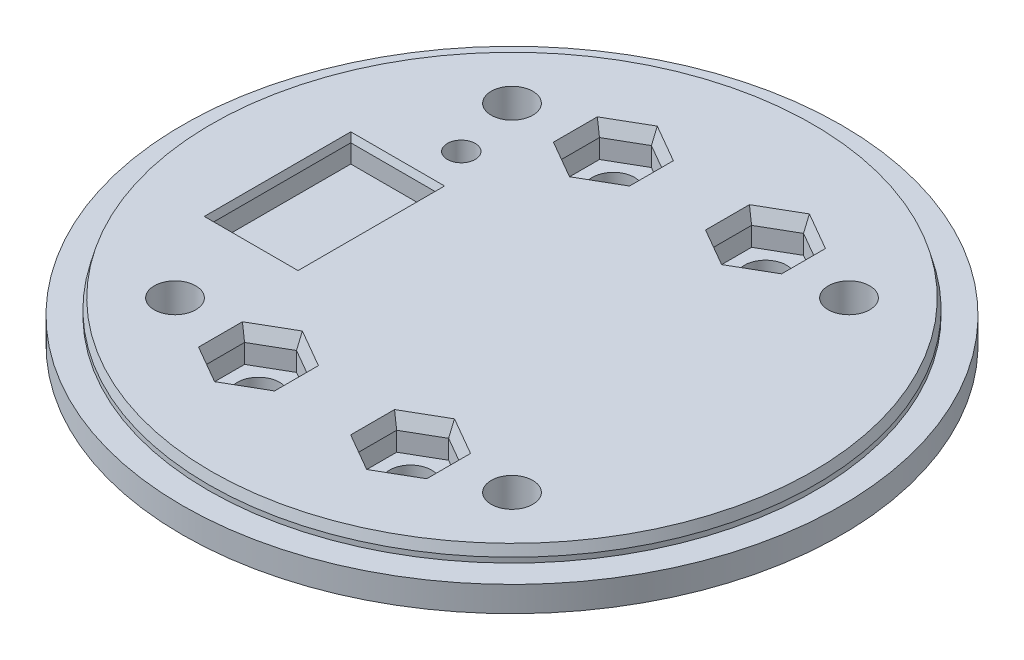
SolidWorks part; units mm, degrees
ref_plane "Спереди" through (0, 0, 0) normal (0, 0, 1) x (1, 0, 0)
ref_plane "Сверху" through (0, 0, 0) normal (0, 1, 0) x (1, 0, 0)
ref_plane "Справа" through (0, 0, 0) normal (1, 0, 0) x (0, 0, -1)
sketch "Эскиз1" plane through (0, 0, 0) normal (0, 1, 0) x (1, 0, 0)
  circle A0 centre (0, 0) radius 65
  dimension "D1" = 130
extrude "Бобышка-Вытянуть1" add sketch "Эскиз1" along normal blind 5
sketch "Эскиз2" plane through (0, 5, 0) normal (0, 1, 0) x (1, 0, 0)
  circle A0 centre (0, 0) radius 59.85
  dimension "D1" = 119.7
extrude "Бобышка-Вытянуть2" add sketch "Эскиз2" along normal blind 3
sketch "Эскиз3" plane through (0, 0, 0) normal (0, -1, 0) x (1, 0, 0)
  line L1 (25, -25) -> (-25, -25)
  line L2 (25, -25) -> (25, 25)
  line L3 (25, 25) -> (-25, 25)
  line L4 (-25, -25) -> (-25, 25)
  line L5 (25, -25) -> (-25, 25) construction
  line L6 (25, 25) -> (-25, -25) construction
  point P0 (0, 0)
  dimension "D1" = 50
  dimension "D2" = 50
extrude "Бобышка-Вытянуть3" add sketch "Эскиз3" along normal blind 25
sketch "Эскиз5" plane through (0, 0, 0) normal (0, -1, 0) x (1, 0, 0)
  line L1 (33.234, -33.234) -> (-33.234, -33.234) construction
  line L2 (33.234, -33.234) -> (33.234, 33.234) construction
  line L3 (33.234, 33.234) -> (-33.234, 33.234) construction
  line L4 (-33.234, -33.234) -> (-33.234, 33.234) construction
  line L5 (33.234, -33.234) -> (-33.234, 33.234) construction
  line L6 (33.234, 33.234) -> (-33.234, -33.234) construction
  circle A1 centre (33.234, -33.234) radius 4.1
  circle A2 centre (-33.234, -33.234) radius 4.1
  circle A3 centre (-33.234, 33.234) radius 4.1
  circle A4 centre (33.234, 33.234) radius 4.1
  circle A5 centre (0, 0) radius 47 construction
  point P0 (0, 0)
  dimension "D1" = 94
  dimension "D2" = 8.2
extrude "Вырез-Вытянуть2" cut sketch "Эскиз5" against normal through all
sketch "Эскиз6" plane through (0, 8, 0) normal (0, 1, 0) x (1, 0, 0)
  line L0 (0, 0) -> (0, 52.4) construction
  line L1 (0, 20) -> (-30, 20) construction
  circle A0 centre (0, 0) radius 59.85 construction
  circle A1 centre (-30, 20) radius 2.75
  dimension "D3" = 5.5
  dimension "D1" = 20
  dimension "D2" = 30
extrude "Вырез-Вытянуть3" cut sketch "Эскиз6" against normal through all
sketch "Sketch2" plane through (-25, 0, 0) normal (-1, 0, 0) x (0, 0, 1)
  line L0 (-25, -25) -> (25, 0) construction
  line L2 (10.125, -17.675) -> (-10.125, -17.675)
  line L3 (10.125, -17.675) -> (10.125, -7.325)
  line L4 (10.125, -7.325) -> (-10.125, -7.325)
  line L5 (-10.125, -17.675) -> (-10.125, -7.325)
  line L6 (10.125, -17.675) -> (-10.125, -7.325) construction
  line L7 (10.125, -7.325) -> (-10.125, -17.675) construction
  point P2 (0, -12.5)
  point P10 (0, -12.5)
  dimension "D1" = 20.25
  dimension "D2" = 10.35
extrude "Cut-Extrude1" cut sketch "Sketch2" against normal through all
chamfer "Chamfer1" distance 2 angle 15 1 edges at (0, 8, 59.85) first distance on face at (0, 8, 59.85)
sketch "Sketch4" plane through (0, -25, 0) normal (0, -1, 0) x (1, 0, 0)
  line L0 (-25, 0) -> (25, 0) construction
  line L1 (-25, 25) -> (-25, -25) construction
  line L2 (25, -25) -> (25, 25) construction
  line L4 (25, -25) -> (-25, -25)
  line L5 (25, -25) -> (25, 25)
  line L6 (25, 25) -> (-25, 25)
  line L7 (-25, -25) -> (-25, 25)
  line L8 (25, -25) -> (-25, 25) construction
  line L9 (25, 25) -> (-25, -25) construction
  point P6 (0, 0)
extrude "Cut-Extrude3" cut sketch "Sketch4" against normal blind 12.5
sketch "Sketch5" plane through (0, -7.325, 0) normal (0, -1, 0) x (1, 0, 0)
  line L0 (0, 10.125) -> (0, -10.125) construction
  line L1 (25, 10.125) -> (-25, 10.125) construction
  line L2 (25, -10.125) -> (-25, -10.125) construction
  line L4 (25, -45) -> (-25, -45)
  line L5 (25, -45) -> (25, 45)
  line L6 (25, 45) -> (-25, 45)
  line L7 (-25, -45) -> (-25, 45)
  line L8 (25, -45) -> (-25, 45) construction
  line L9 (25, 45) -> (-25, -45) construction
  point P6 (0, 0)
  dimension "D1" = 50
  dimension "D2" = 90
extrude "Boss-Extrude2" add sketch "Sketch5" against normal up to surface (7.325 mm away) from offset 2 up to face at (-30, 0, -17.25) offset against normal yes
sketch "Sketch6" plane through (0, -5.325, 0) normal (0, -1, 0) x (1, 0, 0)
  line L0 (25, 35) -> (-25, 35) construction
  line L1 (25, 25) -> (25, 45) construction
  line L2 (-25, 45) -> (-25, 25) construction
  line L3 (25, -35) -> (-25, -35) construction
  line L4 (25, -45) -> (25, -25) construction
  line L5 (-25, -25) -> (-25, -45) construction
  line L6 (0, 45) -> (0, -45) construction
  line L7 (25, 45) -> (-25, 45) construction
  line L8 (-25, -45) -> (25, -45) construction
  line L9 (-15, 35) -> (15, -35) construction
  line L10 (-15, -35) -> (15, 35) construction
  circle A0 centre (-15, 35) radius 4.15
  circle A1 centre (-15, -35) radius 4.15
  circle A2 centre (15, 35) radius 4.15
  circle A3 centre (15, -35) radius 4.15
  point P21 (0, 0)
  point P31 (0, 0)
  dimension "D3" = 8.3
  dimension "D1" = 10
  dimension "D2" = 10
  dimension "D4" = 30
  dimension "D5" = 70
  dimension "D6" = 70
extrude "Cut-Extrude4" cut sketch "Sketch6" against normal through all
sketch "Sketch7" plane through (0, 8, 0) normal (0, 1, 0) x (1, 0, 0)
  line L1 (-15, -42.5) -> (-8.5048, -38.75)
  line L2 (-8.5048, -38.75) -> (-8.5048, -31.25)
  line L3 (-8.5048, -31.25) -> (-15, -27.5)
  line L4 (-15, -27.5) -> (-21.4952, -31.25)
  line L5 (-21.4952, -31.25) -> (-21.4952, -38.75)
  line L6 (-21.4952, -38.75) -> (-15, -42.5)
  line L7 (-15, 27.5) -> (-8.5048, 31.25)
  line L8 (-8.5048, 31.25) -> (-8.5048, 38.75)
  line L9 (-8.5048, 38.75) -> (-15, 42.5)
  line L10 (-15, 42.5) -> (-21.4952, 38.75)
  line L11 (-21.4952, 38.75) -> (-21.4952, 31.25)
  line L12 (-21.4952, 31.25) -> (-15, 27.5)
  line L13 (15, -42.5) -> (21.4952, -38.75)
  line L14 (21.4952, -38.75) -> (21.4952, -31.25)
  line L15 (21.4952, -31.25) -> (15, -27.5)
  line L16 (15, -27.5) -> (8.5048, -31.25)
  line L17 (8.5048, -31.25) -> (8.5048, -38.75)
  line L18 (8.5048, -38.75) -> (15, -42.5)
  line L19 (15, 27.5) -> (21.4952, 31.25)
  line L20 (21.4952, 31.25) -> (21.4952, 38.75)
  line L21 (21.4952, 38.75) -> (15, 42.5)
  line L22 (15, 42.5) -> (8.5048, 38.75)
  line L23 (8.5048, 38.75) -> (8.5048, 31.25)
  line L24 (8.5048, 31.25) -> (15, 27.5)
  circle A0 centre (-15, -35) radius 7.5 construction
  circle A1 centre (-15, 35) radius 7.5 construction
  circle A2 centre (15, -35) radius 7.5 construction
  circle A3 centre (15, 35) radius 7.5 construction
  dimension "D1" = 15
extrude "Cut-Extrude5" cut sketch "Sketch7" against normal blind 6.5
chamfer "Chamfer2" distance 1 angle 70 24 edges at (-11.7524, 8, 29.375) (-8.5048, 8, 35) (-11.7524, 8, 40.625) (-18.2476, 8, 40.625) (-21.4952, 8, 35) (-18.2476, 8, 29.375) (-11.7524, 8, -29.375) (-8.5048, 8, -35) (-11.7524, 8, -40.625) (-18.2476, 8, -40.625) (-21.4952, 8, -35) (-18.2476, 8, -29.375) (11.7524, 8, -40.625) (18.2476, 8, -40.625) (21.4952, 8, -35) (18.2476, 8, -29.375) (11.7524, 8, -29.375) (8.5048, 8, -35) (11.7524, 8, 29.375) (18.2476, 8, 29.375) (21.4952, 8, 35) (18.2476, 8, 40.625) (11.7524, 8, 40.625) (8.5048, 8, 35) first distance on face at (-15, 8, -35)
sketch "Sketch8" plane through (0, 8, 0) normal (0, 1, 0) x (1, 0, 0)
  line L1 (-26.25, 11.95) -> (-43.75, 11.95)
  line L2 (-26.25, 11.95) -> (-26.25, -15.95)
  line L3 (-26.25, -15.95) -> (-43.75, -15.95)
  line L4 (-43.75, 11.95) -> (-43.75, -15.95)
  line L5 (-26.25, 11.95) -> (-43.75, -15.95) construction
  line L6 (-26.25, -15.95) -> (-43.75, 11.95) construction
  point P0 (-35, -2)
  dimension "D1" = 27.9
  dimension "D2" = 17.5
  dimension "D3" = 35
  dimension "D4" = 2
extrude "Cut-Extrude6" cut sketch "Sketch8" against normal blind 5
chamfer "Chamfer3" distance 10 angle 45 4 edges at (25, -2.6625, 45) (25, -2.6625, -45) (-25, -2.6625, -45) (-25, -2.6625, 45)
chamfer "Chamfer4" distance 0.5 angle 70 4 edges at (-43.75, 8, 2) (-35, 8, -11.95) (-35, 8, 15.95) (-26.25, 8, 2) first distance on face at (-35, 8, 2)
chamfer "Chamfer6" distance 3 angle 30 4 edges at (-25, -2.6625, -35) (-25, -2.6625, 35) (25, -2.6625, 35) (25, -2.6625, -35) first distance on face at (-20, -2.6625, -40) first distance on face at (-20, -2.6625, 40) first distance on face at (20, -2.6625, 40) first distance on face at (20, -2.6625, -40)
